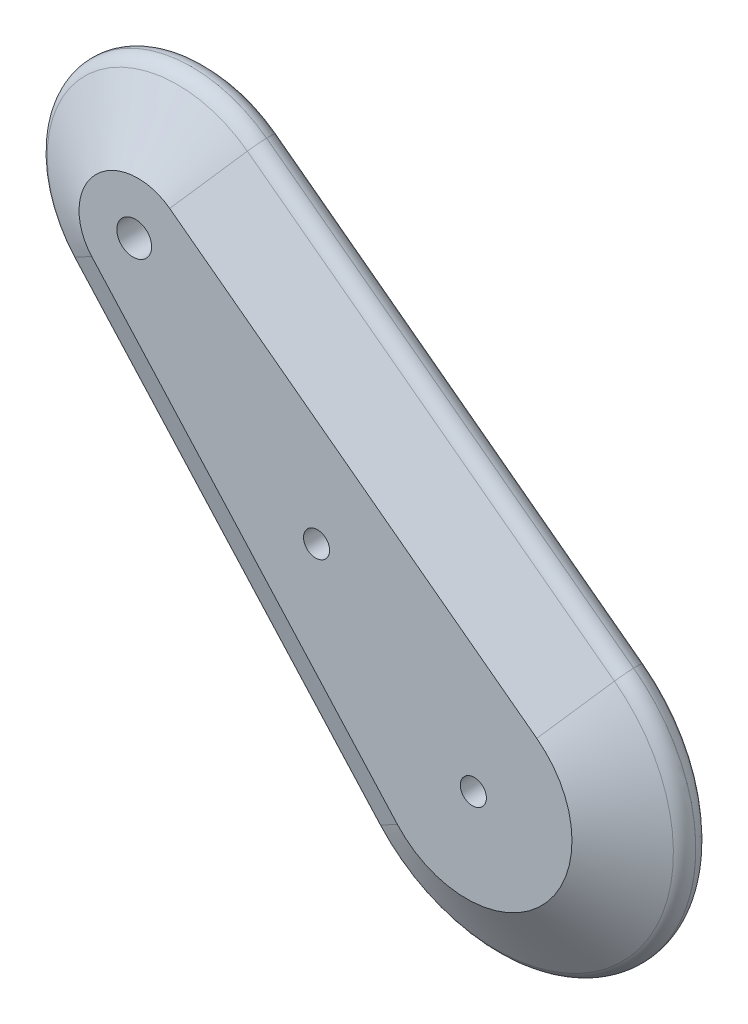
SolidWorks part; units mm, degrees
ref_plane "Front Plane" through (0, 0, 0) normal (0, 0, 1) x (1, 0, 0)
ref_plane "Top Plane" through (0, 0, 0) normal (0, 1, 0) x (1, 0, 0)
ref_plane "Right Plane" through (0, 0, 0) normal (1, 0, 0) x (0, 0, -1)
sketch "Sketch2" plane through (0.6917, 0.3121, 13.788) normal (0.0501, 0.0226, 0.9985) x (0.9987, -0.0011, -0.0501)
  line L0 (191.4232, 115.8214) -> (201.4305, 113.402) construction
  line L1 (201.4305, 113.402) -> (201.7221, 113.3315) construction
  line L2 (171.865, 140.2376) -> (196.9605, 124.855)
  line L3 (165.4838, 133.3093) -> (182.8746, 109.5612)
  circle A2 centre (151.6034, 154.2561) radius 9.8
  circle A3 centre (151.6034, 154.2561) radius 9.8
  arc A5 (182.8746, 109.5612) -> (196.9605, 124.855) centre (191.4232, 115.8214) ccw
  arc A7 (171.865, 140.2376) -> (165.4838, 133.3093) centre (169.3565, 136.1453) ccw
  arc A8 (172.1186, 139.6978) -> (166.0465, 139.1939) centre (169.3565, 136.1453) ccw construction
  dimension "D2" = 0.3
  dimension "D4" = 0.3
  dimension "D1" = 0.3
sketch "Sketch3" plane through (0.6917, 0.3121, 13.788) normal (0.0501, 0.0226, 0.9985) x (0.9987, -0.0011, -0.0501)
  line L1 (140.2537, 144.4487) -> (176.2903, 102.7449)
  line L2 (161.0029, 165.9457) -> (203.9559, 131.4076)
  line L3 (165.4838, 133.3093) -> (182.8746, 109.5612) construction
  line L4 (171.865, 140.2376) -> (196.9605, 124.855) construction
  line L5 (165.4838, 133.3093) -> (182.8746, 109.5612)
  line L6 (171.865, 140.2376) -> (196.9605, 124.855)
  arc A0 (161.0029, 165.9457) -> (140.2537, 144.4487) centre (151.6034, 154.2561) ccw
  arc A1 (176.2903, 102.7449) -> (203.9559, 131.4076) centre (191.4232, 115.8214) ccw
  arc A2 (171.865, 140.2376) -> (165.4838, 133.3093) centre (169.3565, 136.1453) ccw construction
  arc A3 (182.8746, 109.5612) -> (196.9605, 124.855) centre (191.4232, 115.8214) ccw construction
  circle A4 centre (151.6034, 154.2561) radius 9.8 construction
  arc A5 (171.865, 140.2376) -> (165.4838, 133.3093) centre (169.3565, 136.1453) ccw
  arc A6 (182.8746, 109.5612) -> (196.9605, 124.855) centre (191.4232, 115.8214) ccw
  circle A7 centre (151.6034, 154.2561) radius 9.8
  dimension "D1" = 30
  dimension "D2" = 40
extrude "Boss-Extrude1" add sketch "Sketch3" along normal blind 5
sketch "Sketch4" plane through (0.8919, 0.4025, 17.7777) normal (0.0501, 0.0226, 0.9985) x (0.9987, -0.0011, -0.0501)
  circle A0 centre (151.6034, 154.2561) radius 9.8 construction
  circle A1 centre (151.6034, 154.2561) radius 9.8
  circle A2 centre (151.6034, 154.2561) radius 2
  dimension "D1" = 4
extrude "Boss-Extrude2" add sketch "Sketch4" along normal up to surface (1.0042 mm away) from offset 0.5 up to face at (181.6237, 125.6934, 6.8798) offset against normal yes
sketch "Sketch5" plane through (0.9422, 0.4252, 18.7804) normal (0.0501, 0.0226, 0.9985) x (0.9987, -0.0011, -0.0501)
  line L2 (203.9559, 131.4076) -> (161.0029, 165.9457)
  line L3 (140.2537, 144.4487) -> (176.2903, 102.7449)
  line L4 (203.9559, 131.4076) -> (161.0029, 165.9457)
  line L5 (140.2537, 144.4487) -> (176.2903, 102.7449)
  circle A1 centre (151.6034, 154.2561) radius 2
  arc A2 (161.0029, 165.9457) -> (140.2537, 144.4487) centre (151.6034, 154.2561) ccw
  arc A3 (176.2903, 102.7449) -> (203.9559, 131.4076) centre (191.4232, 115.8214) ccw
  arc A4 (161.0029, 165.9457) -> (140.2537, 144.4487) centre (151.6034, 154.2561) ccw
  arc A5 (176.2903, 102.7449) -> (203.9559, 131.4076) centre (191.4232, 115.8214) ccw
  circle A6 centre (191.4232, 115.8214) radius 1.5
  circle A7 centre (173.0343, 132.758) radius 1.5
  circle A8 centre (151.6034, 154.2561) radius 2 construction
  dimension "D2" = 3
  dimension "D1" = 0
extrude "Boss-Extrude3" add sketch "Sketch5" along normal blind 3
chamfer "Chamfer1" distance 1 angle 45 4 edges at (158.765, 123.6978, 3.0642) (206.2467, 101.9844, 1.1737) (141.3257, 164.7836, 3.0091) (182.9421, 148.7438, 1.2843)
chamfer "Chamfer2" distance 5 angle 60 4 edges at (159.1658, 123.8787, 11.0522) (206.6475, 102.1653, 9.1616) (141.7264, 164.9645, 10.997) (183.3428, 148.9247, 9.2722) first distance on face at (158.9904, 123.7996, 7.5574) first distance on face at (198.6369, 109.6654, 5.8884) first distance on face at (146.4537, 160.1429, 7.3637) first distance on face at (183.1675, 148.8456, 5.7775)
fillet "Fillet2" radius 2 8 edges at (206.2968, 102.007, 2.1721) (158.8151, 123.7204, 4.0627) (141.3758, 164.8062, 4.0076) (141.476, 164.8514, 6.0045) (158.9153, 123.7657, 6.0597) (206.397, 102.0522, 4.1691) (182.9922, 148.7664, 2.2828) (183.0924, 148.8117, 4.2798)
fillet "Fillet3" radius 0.5 5 edges at (166.5598, 139.5985, 7.3208) (185.1234, 132.7284, 6.545) (199.909, 108.8147, 6.3446) (162.0676, 154.4358, 5.7038) (174.9028, 121.6319, 7.309)
fillet "Fillet4" radius 1 5 edges at (166.3094, 139.4855, 2.3283) (184.8729, 132.6154, 1.5525) (199.6585, 108.7017, 1.3521) (174.6523, 121.5188, 2.3165) (161.8925, 154.3568, 2.2133)
move or copy body "Body-Move/Copy2" [suppressed] bodies to move or copy 103 parameters "D1"=0, "D2"=0, "D3"=0
move or copy body "Body-Move/Copy1" [suppressed] bodies to move or copy 103 parameters "D1"=0, "D2"=0, "D3"=0
